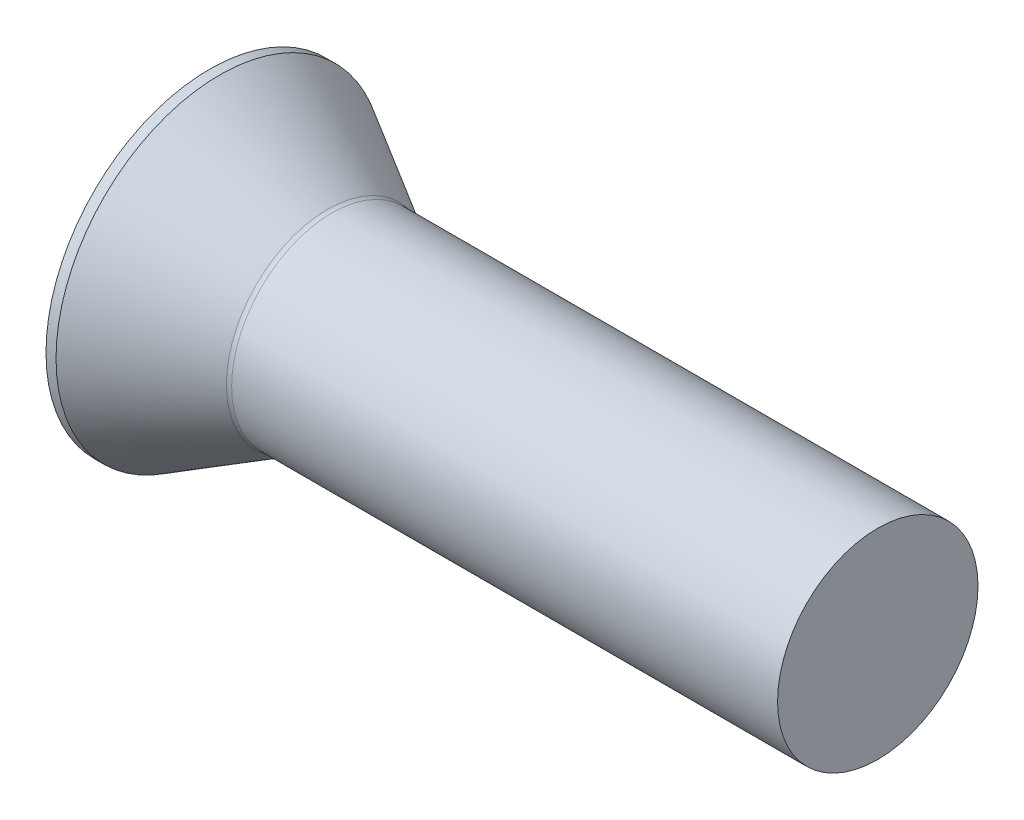
SolidWorks part; units mm, degrees
ref_plane "Front" through (0, 0, 0) normal (0, 0, 1) x (1, 0, 0)
ref_plane "Top" through (0, 0, 0) normal (0, 1, 0) x (1, 0, 0)
ref_plane "Right" through (0, 0, 0) normal (1, 0, 0) x (0, 0, -1)
sketch "Sketch1" plane through (0, 0, 0) normal (0, 0, 1) x (0, 1, 0)
  line L0 (0, 0) -> (9.8, 0)
  line L1 (9.8, 0) -> (9.8, -0.6)
  line L2 (9.8, -0.6) -> (6, -7.1818)
  line L3 (6, -7.1818) -> (6, -40)
  line L4 (6, -40) -> (0, -40)
  line L5 (0, -40) -> (0, 0)
  line L6 (0, 2.03) -> (0, -4.03) construction
  dimension "b" = 0.6
  dimension "dk" = 19.6
  dimension "l" = 40
  dimension "d" = 12
  dimension "a" = 30
revolve "Base-Revolve" add sketch "Sketch1" angle 360 about L6
fillet "Fillet1" radius 0.5 1 edges at (7.1818, 0, 6)
